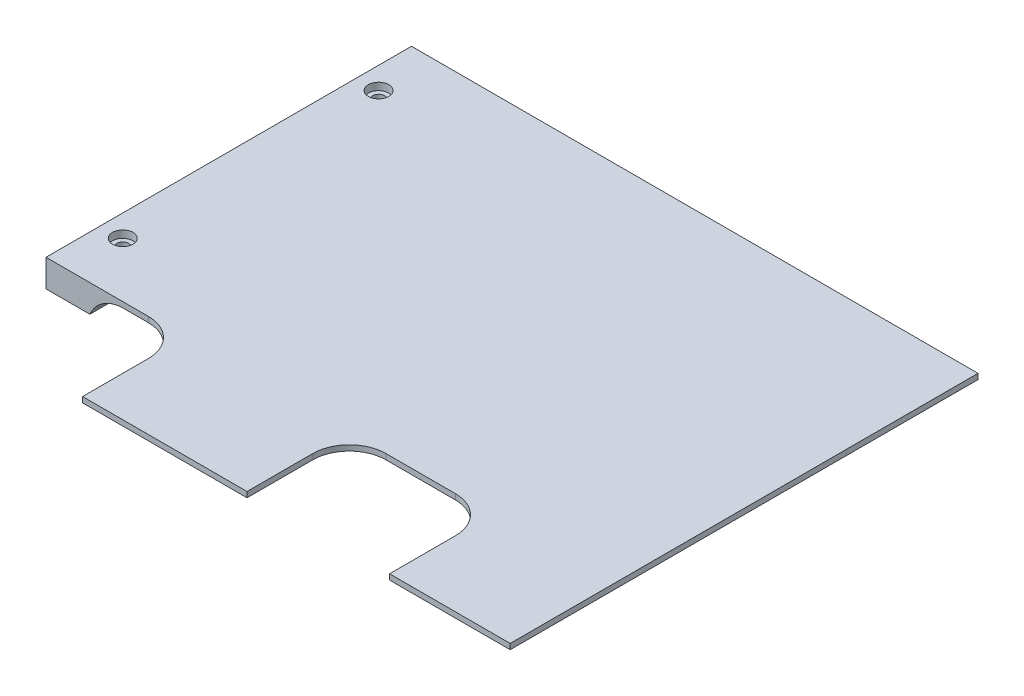
SolidWorks part; units mm, degrees
ref_plane "Alzado" through (0, 0, 0) normal (0, 0, 1) x (1, 0, 0)
ref_plane "Planta" through (0, 0, 0) normal (0, 1, 0) x (1, 0, 0)
ref_plane "Vista lateral" through (0, 0, 0) normal (1, 0, 0) x (0, 0, -1)
sketch "Croquis1" plane through (0, 0, 0) normal (0, 1, 0) x (1, 0, 0)
  line L1 (0, 0) -> (155, 0)
  line L2 (0, 0) -> (0, 100)
  line L3 (0, 100) -> (155, 100)
  line L4 (155, 0) -> (155, 100)
  dimension "D1" = 155
  dimension "D2" = 100
extrude "Saliente-Extruir1" add sketch "Croquis1" along normal blind 1.5
sketch "Croquis2" plane through (0, 1.5, 0) normal (0, 1, 0) x (1, 0, 0)
  line L0 (6, 100) -> (6, 0) construction
  line L1 (155, 100) -> (0, 100) construction
  line L2 (0, 0) -> (155, 0) construction
  line L3 (0, 100) -> (0, 0) construction
  circle A0 centre (6, 85) radius 1.6
  circle A1 centre (6, 15) radius 1.6
  dimension "D2" = 3.2
  dimension "D3" = 3.2
  dimension "D1" = 6
  dimension "D4" = 15
  dimension "D5" = 15
extrude "Cortar-Extruir1" cut sketch "Croquis2" against normal up to surface (1.5 mm away) up to face at (77.5, 0, -50)
sketch "Croquis3" plane through (0, 0, 0) normal (0, -1, 0) x (1, 0, 0)
  line L0 (0, 0) -> (155, 0) construction
  line L1 (0, -100) -> (12, -100)
  line L2 (0, -100) -> (0, 0)
  line L3 (0, 0) -> (12, 0)
  line L4 (12, -100) -> (12, 0)
  circle A0 centre (6, -15) radius 1.6 construction
  circle A1 centre (6, -85) radius 1.6 construction
  circle A2 centre (6, -15) radius 1.6
  circle A3 centre (6, -85) radius 1.6
  dimension "D1" = 12
extrude "Saliente-Extruir2" add sketch "Croquis3" along normal blind 6
sketch "Croquis4" plane through (0, 1.5, 0) normal (0, 1, 0) x (1, 0, 0)
  line L0 (0, 0) -> (155, 0) construction
  line L1 (38, 0) -> (83, 0)
  line L2 (38, 0) -> (38, -28)
  line L3 (38, -28) -> (83, -28)
  line L4 (83, 0) -> (83, -28)
  line L5 (0, 100) -> (0, 0) construction
  line L6 (155, 0) -> (122, 0)
  line L7 (155, 0) -> (155, -28)
  line L8 (155, -28) -> (122, -28)
  line L9 (122, 0) -> (122, -28)
  point P11 (121.0195, -30.9442)
  point P12 (88.0141, -30.9442)
  point P13 (28.05, -31.1961)
  point P14 (0, 0)
  point P15 (88.4453, -30)
  point P16 (0, 0)
  point P19 (88, -30)
  point P20 (0, 0)
  dimension "D1" = 28
  dimension "D2" = 28
  dimension "D3" = 38
  dimension "D4" = 33
  dimension "D5" = 45
extrude "Saliente-Extruir3" add sketch "Croquis4" against normal up to surface (1.5 mm away) up to face at (83.5, 0, -50)
fillet "Redondeo1" radius 10 3 edges at (38, 0.75, 0) (83, 0.75, 0) (122, 0.75, 0)
fillet "Redondeo2" radius 10 1 edges at (12, 0, -50)
sketch "Croquis5" plane through (0, 1.5, 0) normal (0, 1, 0) x (1, 0, 0)
  circle A0 centre (6, 85) radius 2.8
  circle A1 centre (6, 15) radius 2.8
  dimension "D1" = 5.6
  dimension "D2" = 5.6
extrude "Cortar-Extruir2" cut sketch "Croquis5" against normal blind 2
